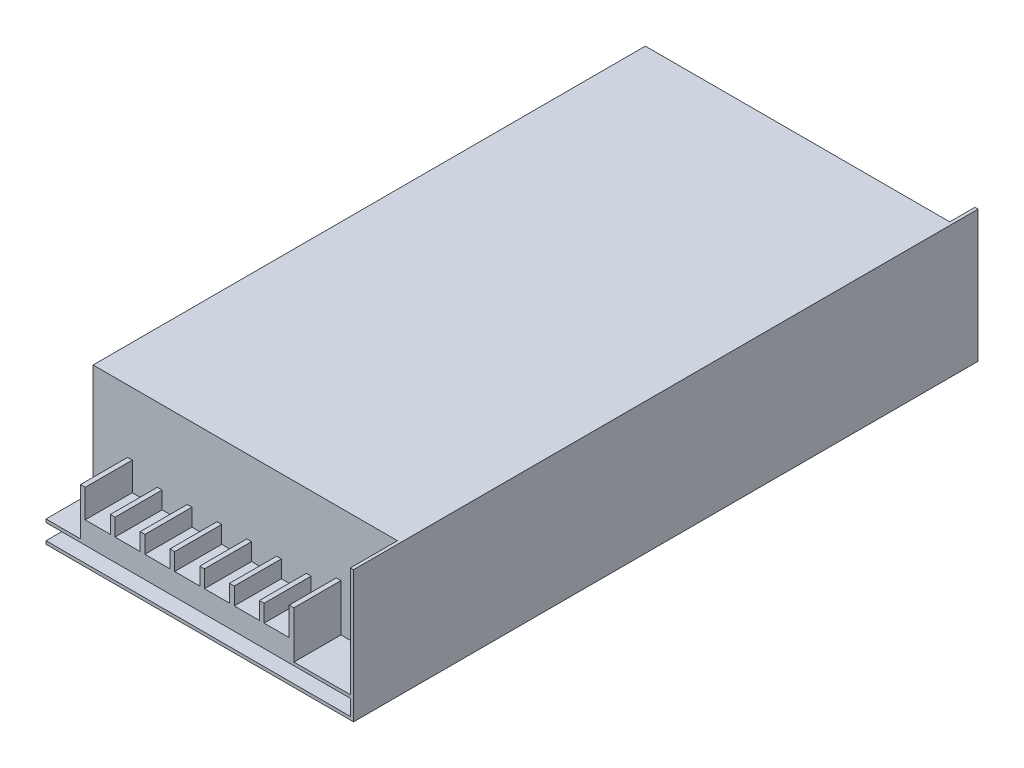
SolidWorks part; units mm, degrees
ref_plane "Front Plane" through (0, 0, 0) normal (0, 0, 1) x (1, 0, 0)
ref_plane "Top Plane" through (0, 0, 0) normal (0, 1, 0) x (1, 0, 0)
ref_plane "Right Plane" through (0, 0, 0) normal (1, 0, 0) x (0, 0, -1)
sketch "Sketch1" plane through (0, 0, 0) normal (0, 1, 0) x (1, 0, 0)
  line L1 (49, -99.5) -> (-49, -99.5)
  line L2 (49, -99.5) -> (49, 99.5)
  line L3 (49, 99.5) -> (-49, 99.5)
  line L4 (-49, -99.5) -> (-49, 99.5)
  line L5 (49, -99.5) -> (-49, 99.5) construction
  line L6 (49, 99.5) -> (-49, -99.5) construction
  point P0 (0, 0)
extrude "Boss-Extrude1" add sketch "Sketch1" along normal blind 42 contours L4 L3 L2 L1
sketch "Sketch3" plane through (0, 0, 0) normal (0, -1, 0) x (1, 0, 0)
  line L0 (-40.5, -99.5) -> (-40.5, -81.5) construction
  line L1 (49, -99.5) -> (-49, -99.5) construction
  line L2 (-49, -81.5) -> (-40.5, -81.5) construction
  line L3 (-49, 99.5) -> (-49, -99.5) construction
  line L4 (-40.5, -81.5) -> (39.5, -81.5) construction
  line L5 (39.5, -99.5) -> (39.5, -81.5) construction
  line L6 (39.5, -81.5) -> (49, -81.5) construction
  line L7 (49, 99.5) -> (49, -99.5) construction
  line L8 (-40.5, -81.5) -> (-40.5, 38.5) construction
  line L9 (-40.5, 38.5) -> (39.5, 38.5) construction
  line L10 (39.5, 38.5) -> (39.5, -81.5) construction
  circle A0 centre (-40.5, 38.5) radius 1.5
  circle A1 centre (39.5, 38.5) radius 1.5
  circle A2 centre (-40.5, -81.5) radius 1.5
  circle A3 centre (39.5, -81.5) radius 1.5
extrude "Cut-Extrude1" cut sketch "Sketch3" against normal blind 3
sketch "Sketch4" plane through (0, 42, 0) normal (0, 1, 0) x (1, 0, 0)
  line L0 (49, 99.5) -> (48, 99.5) construction
  line L1 (49, 99.5) -> (-49, 99.5) construction
  line L2 (48, 99.5) -> (-49, 99.5)
  line L3 (-49, 99.5) -> (-49, 91.5)
  line L4 (-49, -99.5) -> (-49, 99.5) construction
  line L5 (-49, 91.5) -> (48, 91.5)
  line L6 (48, 91.5) -> (48, 99.5)
  point P5 (0, 0)
extrude "Cut-Extrude2" cut sketch "Sketch4" against normal blind 41
sketch "Sketch5" plane through (0, 42, 0) normal (0, 1, 0) x (1, 0, 0)
  line L0 (49, -99.5) -> (48, -99.5) construction
  line L1 (49, -99.5) -> (-49, -99.5) construction
  line L2 (48, -99.5) -> (48, -84.5)
  line L3 (48, -84.5) -> (-49, -84.5)
  line L4 (-49, -99.5) -> (-49, 91.5) construction
  line L5 (-49, -84.5) -> (-49, -99.5)
  line L6 (-49, -99.5) -> (48, -99.5)
extrude "Cut-Extrude3" cut sketch "Sketch5" against normal blind 41
sketch "Sketch6" plane through (0, 0, 84.5) normal (0, 0, 1) x (1, 0, 0)
  line L0 (-49, 1) -> (-49, 6) construction
  line L1 (-49, 1) -> (-49, 42) construction
  line L2 (-49, 6) -> (48, 6)
  line L3 (48, 1) -> (48, 42) construction
  line L4 (48, 6) -> (48, 7)
  line L5 (48, 7) -> (30, 7)
  line L6 (-49, 7) -> (-49, 6)
  line L7 (-49, 9.6476) -> (-38, 9.6476) construction
  line L8 (-38, 7) -> (-38, 13)
  line L9 (-38, 13) -> (-38, 22)
  line L10 (-36.5, 13) -> (-28.5, 13)
  line L11 (30, 13) -> (48, 13) construction
  line L12 (30, 13) -> (30, 7)
  line L13 (-38, 22) -> (-36.5, 22)
  line L14 (-36.5, 22) -> (-36.5, 13)
  line L15 (-36.5, 17.5) -> (-28.5, 17.5) construction
  line L16 (-28.5, 13) -> (-28.5, 18.5)
  line L17 (-28.5, 18.5) -> (-27, 18.5)
  line L18 (-27, 18.5) -> (-27, 13)
  line L19 (-19, 13) -> (-19, 18.5)
  line L20 (-19, 18.5) -> (-17.5, 18.5)
  line L21 (-17.5, 18.5) -> (-17.5, 13)
  line L22 (-27, 17.5) -> (-19, 17.5) construction
  line L23 (-9.5, 13) -> (-9.5, 18.5)
  line L24 (-9.5, 18.5) -> (-8, 18.5)
  line L25 (-8, 18.5) -> (-8, 13)
  line L26 (-17.5, 17.5) -> (-9.5, 17.5) construction
  line L27 (0, 13) -> (0, 18.5)
  line L28 (0, 18.5) -> (1.5, 18.5)
  line L29 (1.5, 18.5) -> (1.5, 13)
  line L30 (-8, 17.5) -> (0, 17.5) construction
  line L31 (9.5, 13) -> (9.5, 18.5)
  line L32 (9.5, 18.5) -> (11, 18.5)
  line L33 (11, 18.5) -> (11, 13)
  line L34 (1.5, 17.5) -> (9.5, 17.5) construction
  line L35 (19, 13) -> (19, 18.5)
  line L36 (19, 18.5) -> (20.5, 18.5)
  line L37 (20.5, 18.5) -> (20.5, 13)
  line L38 (11, 17.5) -> (19, 17.5) construction
  line L42 (20.5, 17.5) -> (28.5, 17.5) construction
  line L43 (30, 18.5) -> (30, 13) [skipped]
  line L44 (-38, 7) -> (-49, 7)
  line L45 (-27, 13) -> (-19, 13)
  line L46 (-17.5, 13) -> (-9.5, 13)
  line L47 (-8, 13) -> (0, 13)
  line L48 (1.5, 13) -> (9.5, 13)
  line L49 (11, 13) -> (19, 13)
  line L50 (20.5, 13) -> (28.5, 13)
  line L51 (28.5, 18.5) -> (30, 18.5) [skipped]
  line L52 (28.5, 13) -> (28.5, 18.5) [skipped]
  line L53 (30, 13) -> (30, 22)
  line L54 (30, 22) -> (28.5, 22)
  line L55 (28.5, 22) -> (28.5, 13)
  dimension "D1" = 1
  dimension "D2" = 5
  dimension "D3" = 7
extrude "Boss-Extrude2" add sketch "Sketch6" along normal blind 15
